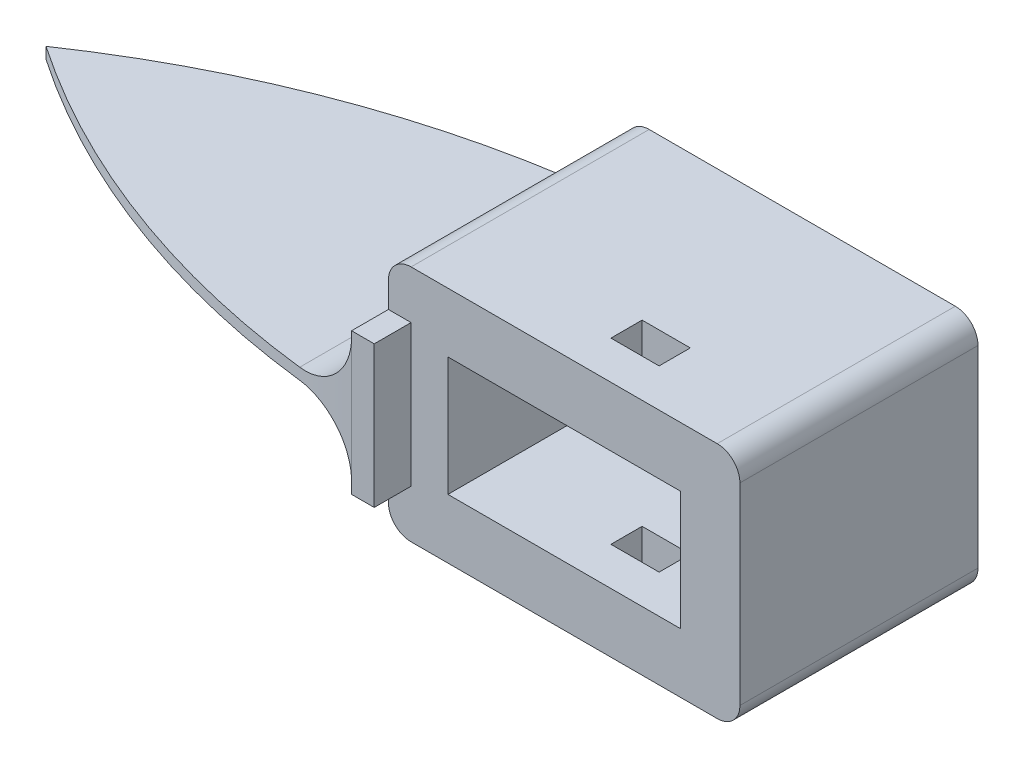
SolidWorks part; units mm, degrees
ref_plane "前基準面" through (0, 0, 0) normal (0, 0, 1) x (1, 0, 0)
ref_plane "上基準面" through (0, 0, 0) normal (0, 1, 0) x (1, 0, 0)
ref_plane "右基準面" through (0, 0, 0) normal (1, 0, 0) x (0, 0, -1)
sketch "Sketch1" plane through (0, 0, 0) normal (0, 0, 1) x (1, 0, 0)
  line L0 (-29.0958, -4.1361) -> (32.9042, -4.1361) construction
  line L1 (-18.5958, 6.3639) -> (22.4042, 6.3639)
  line L2 (-18.5958, 6.3639) -> (-18.5958, -14.6361)
  line L3 (-18.5958, -14.6361) -> (22.4042, -14.6361)
  line L4 (22.4042, 6.3639) -> (22.4042, -14.6361)
  line L5 (-29.0958, 16.8639) -> (32.9042, 16.8639)
  line L6 (-29.0958, 16.8639) -> (-29.0958, -25.1361)
  line L7 (-29.0958, -25.1361) -> (32.9042, -25.1361)
  line L8 (32.9042, 16.8639) -> (32.9042, -25.1361)
  line L9 (1.9042, 16.8639) -> (1.9042, -25.1361) construction
  line L10 (22.4042, -4.1361) -> (-18.5958, -4.1361) construction
  line L11 (1.9042, 6.3639) -> (1.9042, -14.6361) construction
  point P16 (1.9042, -4.1361)
  point P17 (1.9042, -4.1361)
  dimension "D1" = 21
  dimension "D2" = 41
  dimension "D3" = 62
  dimension "D4" = 42
extrude "Boss-Extrude1" add sketch "Sketch1" along normal blind 42
sketch "Sketch2" plane through (0, 0, 42) normal (0, 0, 1) x (1, 0, 0)
  line L0 (-18.5958, -4.1361) -> (-29.0958, -4.1361) construction
  line L1 (-25.0958, -4.1361) -> (-29.0958, -4.1361) construction
  line L3 (-29.0958, 16.8639) -> (-29.0958, -25.1361) construction
  line L4 (-18.5958, 6.3639) -> (-18.5958, -14.6361) construction
  line L5 (-29.0958, 8.3639) -> (-25.0958, 8.3639)
  line L6 (-29.0958, 8.3639) -> (-29.0958, -16.6361)
  line L7 (-29.0958, -16.6361) -> (-25.0958, -16.6361)
  line L8 (-25.0958, 8.3639) -> (-25.0958, -16.6361)
  dimension "D1" = 25
  dimension "D2" = 4
extrude "Boss-Extrude2" add sketch "Sketch2" along normal blind 4.5
extrude "Boss-Extrude3" add sketch "Sketch2<2>" against normal blind 45.55
sketch "Sketch2<2>" plane through (0, 0, 42) normal (0, 0, 1) x (1, 0, 0) same geometry as "Sketch2"
sketch "Sketch3" plane through (0, 0, 46.5) normal (0, 0, 1) x (1, 0, 0)
  line L0 (-60.5958, 2.9639) -> (-59.5958, 2.9639) construction
  line L1 (-25.0958, 8.3639) -> (-60.0958, 8.3639)
  line L2 (-25.0958, 8.3639) -> (-25.0958, -16.6361)
  line L3 (-25.0958, -16.6361) -> (-60.0958, -16.6361)
  line L4 (-60.0958, 8.3639) -> (-60.0958, -16.6361)
  line L5 (-60.5958, 4.4639) -> (-59.5958, 4.4639)
  line L6 (-60.5958, 1.4639) -> (-59.5958, 1.4639)
  line L7 (-60.0958, 8.3639) -> (-60.0958, -16.6361) construction
  line L8 (-60.5559, -11.6762) -> (-59.6357, -11.6762) construction
  line L9 (-60.5559, -10.1762) -> (-59.6357, -10.1762)
  line L10 (-60.5559, -13.1762) -> (-59.6357, -13.1762)
  line L11 (-60.0958, -4.1361) -> (-72.5958, -4.1361) construction
  line L12 (-67.1958, -3.6361) -> (-67.1958, -4.6361) construction
  line L15 (-65.6958, -3.6361) -> (-65.6958, -4.6361)
  line L16 (-68.6958, -3.6361) -> (-68.6958, -4.6361)
  line L17 (-52.9958, -3.6361) -> (-52.9958, -4.6361) construction
  line L18 (-51.4958, -3.6361) -> (-51.4958, -4.6361)
  line L19 (-54.4958, -3.6361) -> (-54.4958, -4.6361)
  line L20 (-60.0958, -4.1361) -> (-25.0958, -4.1361) construction
  line L21 (-29.0958, 8.3639) -> (-29.0958, -16.6361) construction
  arc A0 (-60.0958, 8.3639) -> (-60.0958, -16.6361) centre (-60.0958, -4.1361) ccw
  circle A1 centre (-60.0958, -4.1361) radius 4.05
  arc A3 (-60.5958, 4.4639) -> (-60.5958, 1.4639) centre (-60.5958, 2.9639) ccw
  arc A4 (-59.5958, 1.4639) -> (-59.5958, 4.4639) centre (-59.5958, 2.9639) ccw
  arc A5 (-60.5559, -10.1762) -> (-60.5559, -13.1762) centre (-60.5559, -11.6762) ccw
  arc A6 (-59.6357, -13.1762) -> (-59.6357, -10.1762) centre (-59.6357, -11.6762) ccw
  arc A9 (-65.6958, -3.6361) -> (-68.6958, -3.6361) centre (-67.1958, -3.6361) ccw
  arc A10 (-68.6958, -4.6361) -> (-65.6958, -4.6361) centre (-67.1958, -4.6361) ccw
  arc A11 (-51.4958, -3.6361) -> (-54.4958, -3.6361) centre (-52.9958, -3.6361) ccw
  arc A12 (-54.4958, -4.6361) -> (-51.4958, -4.6361) centre (-52.9958, -4.6361) ccw
  point P9 (-60.0958, 2.9639)
  point P14 (-58.0958, 2.9639)
  point P15 (-62.0958, 2.9639)
  point P19 (-60.0958, -11.6762)
  point P25 (-67.1958, -4.1361)
  point P31 (-67.1958, -2.1361)
  point P32 (-67.1958, -6.1361)
  point P34 (-65.6958, -4.1361)
  point P37 (-52.9958, -4.1361)
  point P42 (-52.9958, -2.1361)
  point P43 (-52.9958, -6.1361)
  line M15 (-29.0958, 8.3639) -> (-29.0958, -16.6361)
  line M16 (-29.0958, -16.6361) -> (-25.0958, -16.6361)
  line M17 (-25.0958, -16.6361) -> (-25.0958, 8.3639)
  line M18 (-25.0958, 8.3639) -> (-29.0958, 8.3639)
  dimension "D2" = 4
  dimension "D10" = 5.6
  dimension "D9" = 4
  dimension "D3" = 3
  dimension "D4" = 5.6
  dimension "D5" = 25
  dimension "D6" = 6.0402
  dimension "D7" = 0
  dimension "D8" = 3
  dimension "D11" = 5.6
  dimension "D12" = 3
  dimension "D13" = 4
  dimension "D14" = 31
extrude "Boss-Extrude6" add sketch "Sketch3" along normal blind 2 contours A5 L9 L4 A1 L6 A3 L5 A0 L10 A10 L16 A9 L15 | A6 L10 L4 L3 L1 L5 A4 L6 A1 L9 A12 L19 A11 L18 M15 | M18 M15 M16 M17 region at (-27.0958, -4.1361, 46.5) region at (-43.7932, -4.1343, 46.5) region at (-60.3753, 6.4139, 46.5)
extrude "Boss-Extrude7" add sketch "Sketch3<8>" against normal blind 53 contours A5 L9 L4 A1 L6 A3 L5 A0 L10 A10 L16 A9 L15 | A6 L10 L4 L3 L1 L5 A4 L6 A1 L9 A12 L19 A11 L18 M15 | M18 M15 M16 M17 region at (-27.0958, -4.1361, 46.5) region at (-43.7932, -4.1343, 46.5) region at (-60.3753, 6.4139, 46.5)
sketch "Sketch3<8>" plane through (0, 0, 46.5) normal (0, 0, 1) x (1, 0, 0) same geometry as "Sketch3"
extrude "Cut-Extrude1" cut sketch "Sketch3<11>" against normal blind 51 contours A6 L10 L4 L3 L1 L5 A4 L6 A1 L9 A12 L19 A11 L18 M15 | A5 L9 L4 A1 L6 A3 L5 A0 L10 A10 L16 A9 L15 region at (-43.7932, -4.1343, 46.5) region at (-60.3753, 6.4139, 46.5)
sketch "Sketch3<11>" plane through (0, 0, 46.5) normal (0, 0, 1) x (1, 0, 0) same geometry as "Sketch3"
sketch "草圖1" plane through (0, 16.8639, 0) normal (0, 1, 0) x (1, 0, 0)
  line L1 (11.9042, -35.25) -> (3.4042, -35.25)
  line L2 (11.9042, -35.25) -> (11.9042, -29.75)
  line L3 (11.9042, -29.75) -> (3.4042, -29.75)
  line L4 (3.4042, -35.25) -> (3.4042, -29.75)
  line L5 (32.9042, -42) -> (-29.0958, -42) construction
  line L7 (22.4042, -42) -> (22.4042, 0) construction
  dimension "D1" = 8.5
  dimension "D2" = 5.5
  dimension "D3" = 10.5
  dimension "D4" = 6.75
extrude "除料-伸長1" cut sketch "草圖1" against normal blind 42
fillet "圓角3" radius 4 1 edges at (-29.0958, 16.8639, 21) type face fillet first side face at (7.6542, 16.8639, 32.5) second side face at (-29.0958, -4.1361, 21)
fillet "圓角4" radius 4 1 edges at (32.9042, 16.8639, 21) type face fillet first side face at (7.6542, 16.8639, 32.5) second side face at (32.9042, -4.1361, 21)
fillet "圓角5" radius 4 1 edges at (32.9042, -25.1361, 21) type face fillet first side face at (7.6542, -25.1361, 32.5) second side face at (32.9042, -6.1361, 21)
fillet "圓角6" radius 4 1 edges at (-29.0958, -25.1361, 21) type face fillet first side face at (7.6542, -25.1361, 32.5) second side face at (-29.0958, -4.8027, 21)
sketch "Sketch8" plane through (0, 0, -6.5) normal (0, 0, -1) x (-1, 0, 0)
  line L0 (29.0958, 8.3639) -> (72.6806, 8.3639)
  line L1 (72.6806, 8.3639) -> (72.6806, -16.7421)
  line L2 (72.6806, -16.7421) -> (29.0958, -16.6361)
  line L3 (29.0958, -16.6361) -> (29.0958, 8.3639)
extrude "Cut-Extrude3" cut sketch "Sketch8" against normal blind 55
sketch "Sketch9" plane through (0, 16.8639, 0) normal (0, 1, 0) x (1, 0, 0)
  line L0 (-29.0958, 6.5) -> (-29.0958, -48.5)
  line L1 (-29.0958, -21) -> (-110.4942, -21)
  arc A0 (-29.0958, 6.5) -> (-110.4942, -21) centre (-20.464, -153.267) ccw
  arc A1 (-110.4942, -21) -> (-29.0958, -48.5) centre (-20.464, 111.267) ccw
extrude "Boss-Extrude8" add sketch "Sketch9" against normal blind 21.5 contours L0 A0 L1 | L1 A1 L0 region at (-59.5483, 16.8639, 10.2538) region at (-59.5483, 16.8639, 31.7462)
extrude "Cut-Extrude4" cut sketch "Sketch9<4>" against normal blind 19.5 contours L0 A0 L1 | L1 A1 L0 region at (-59.5483, 16.8639, 10.2538) region at (-59.5483, 16.8639, 31.7462)
sketch "Sketch9<4>" plane through (0, 16.8639, 0) normal (0, 1, 0) x (1, 0, 0) same geometry as "Sketch9"
fillet "圓角7" radius 10 1 edges at (-29.0958, -4.6361, 21) type face fillet first side face at (-29.0958, -14.7611, 21) second side face at (-57.4822, -4.6361, 21)
fillet "圓角8" radius 10 1 edges at (-29.0958, -2.6361, 21) type face fillet first side face at (-29.0958, 6.7389, 21) second side face at (-57.4822, -2.6361, 21)
